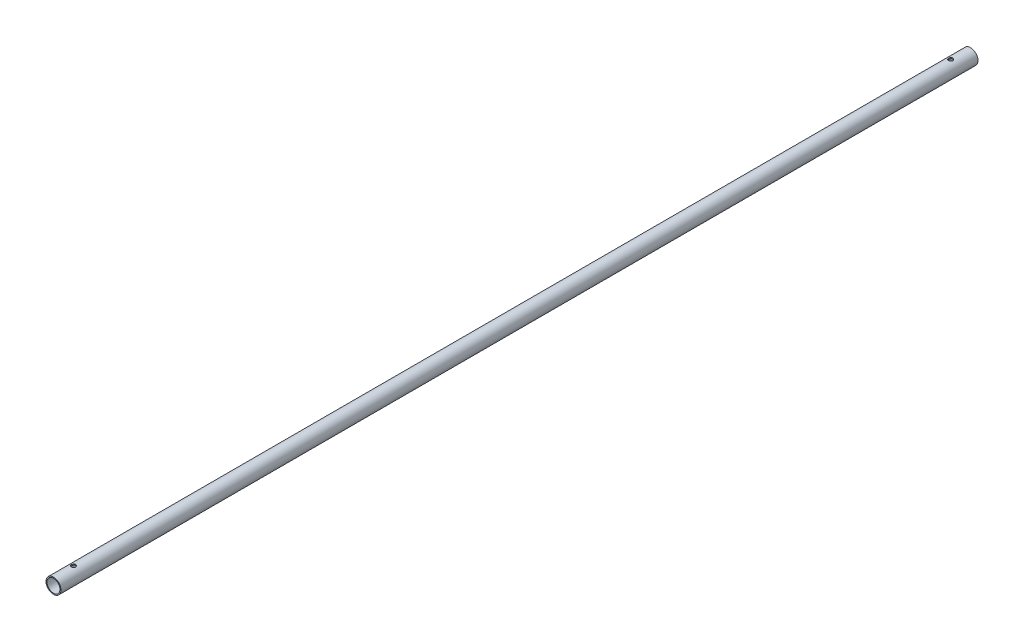
SolidWorks part; units mm, degrees
ref_plane "Front Plane" through (0, 0, 0) normal (0, 0, 1) x (1, 0, 0)
ref_plane "Top Plane" through (0, 0, 0) normal (0, 1, 0) x (1, 0, 0)
ref_plane "Right Plane" through (0, 0, 0) normal (1, 0, 0) x (0, 0, -1)
sketch "Sketch1" plane through (0, 0, 0) normal (0, 0, 1) x (1, 0, 0)
  circle A0 centre (0, 0) radius 19.05
  dimension "D1" = 38.1
extrude "Extrude-Thin1" add sketch "Sketch1" against normal up to surface (2336.8 mm away) thin thin type one direction reverse wall 2.54
sketch "Sketch2" plane through (0, 0, 0) normal (0, 1, 0) x (1, 0, 0)
  line L0 (0, 50.8) -> (0, 0) construction
  line L1 (0, 2336.8) -> (0, 2286) construction
  line L2 (19.05, 2336.8) -> (-19.05, 2336.8) construction
  circle A0 centre (0, 50.8) radius 5.5563
  circle A1 centre (0, 2286) radius 5.5562
  dimension "D1" = 11.1125
  dimension "D2" = 50.8
extrude "Cut-Extrude1" cut sketch "Sketch2" along normal through all
